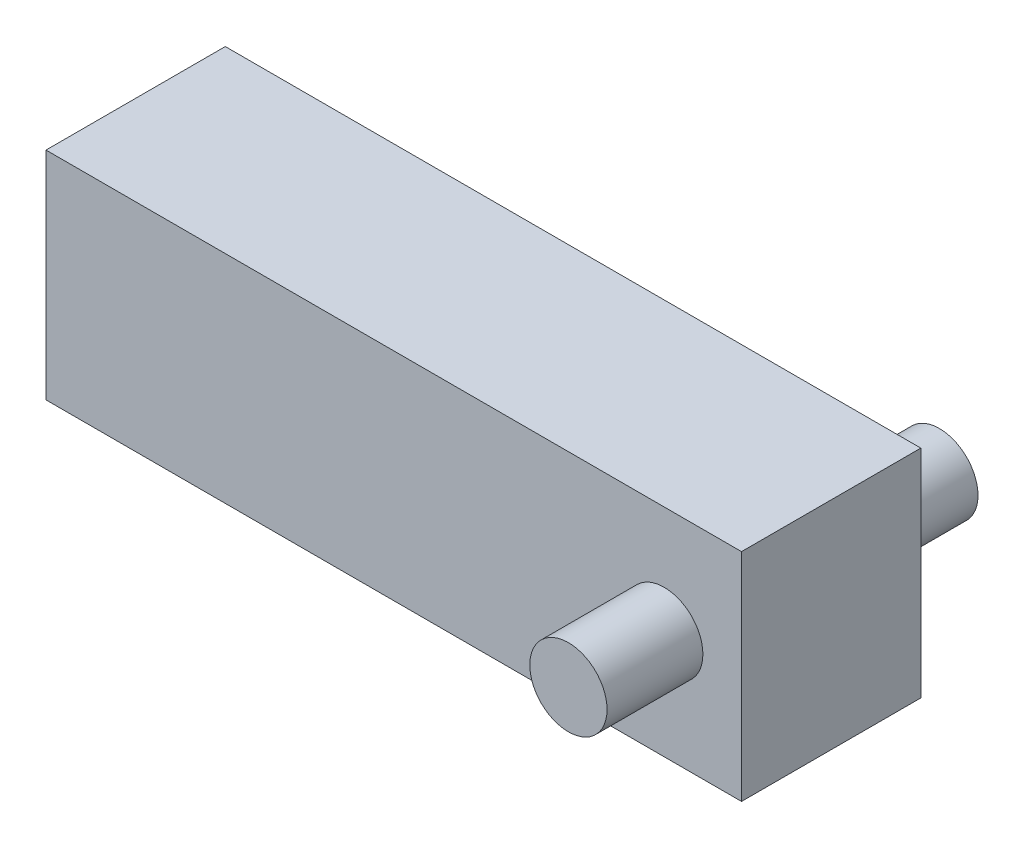
SolidWorks part; units mm, degrees
ref_plane "Front Plane" through (0, 0, 0) normal (0, 0, 1) x (1, 0, 0)
ref_plane "Top Plane" through (0, 0, 0) normal (0, 1, 0) x (1, 0, 0)
ref_plane "Right Plane" through (0, 0, 0) normal (1, 0, 0) x (0, 0, -1)
sketch "Sketch1" plane through (0, 0, 0) normal (0, 0, 1) x (1, 0, 0)
  line L0 (-12.7, 0) -> (12.7, 0) construction
  line L1 (0, -4.445) -> (0, 4.445) construction
  line L2 (-12.7, 4.445) -> (12.7, 4.445)
  line L3 (12.7, 4.445) -> (15.875, 4.445)
  line L4 (12.7, -4.445) -> (-12.7, -4.445)
  line L5 (-12.7, -4.445) -> (-12.7, 4.445)
  line L6 (15.875, 4.445) -> (15.875, -4.445)
  line L7 (15.875, -4.445) -> (12.7, -4.445)
  arc A0 (12.7, 4.445) -> (12.7, -4.445) centre (12.7, 0) cw construction
  dimension "D1" = 25.4
  dimension "D2" = 8.89
  dimension "D3" = 28.575
extrude "Extrude1" add sketch "Sketch1" along normal blind 3.683 and the other way blind 3.683
sketch "Sketch4" plane through (0, 0, 0) normal (0, 0, 1) x (1, 0, 0)
  line L0 (12.7, 4.445) -> (12.7, -4.445) construction
  line L1 (4.5339, 4.445) -> (4.5339, -4.445) construction
  line L2 (15.875, 4.445) -> (-12.7, 4.445) construction
  line L3 (-12.7, -4.445) -> (15.875, -4.445) construction
  line L4 (15.875, 4.445) -> (-12.7, 4.445) construction
  line L5 (-12.7, -4.445) -> (15.875, -4.445) construction
  circle A1 centre (12.7, 0) radius 1.5875
  dimension "D3" = 3.175
  dimension "D1" = 8.1661
extrude "Boss-Extrude1" add sketch "Sketch4" along normal blind 7.62 and the other way blind 7.62
